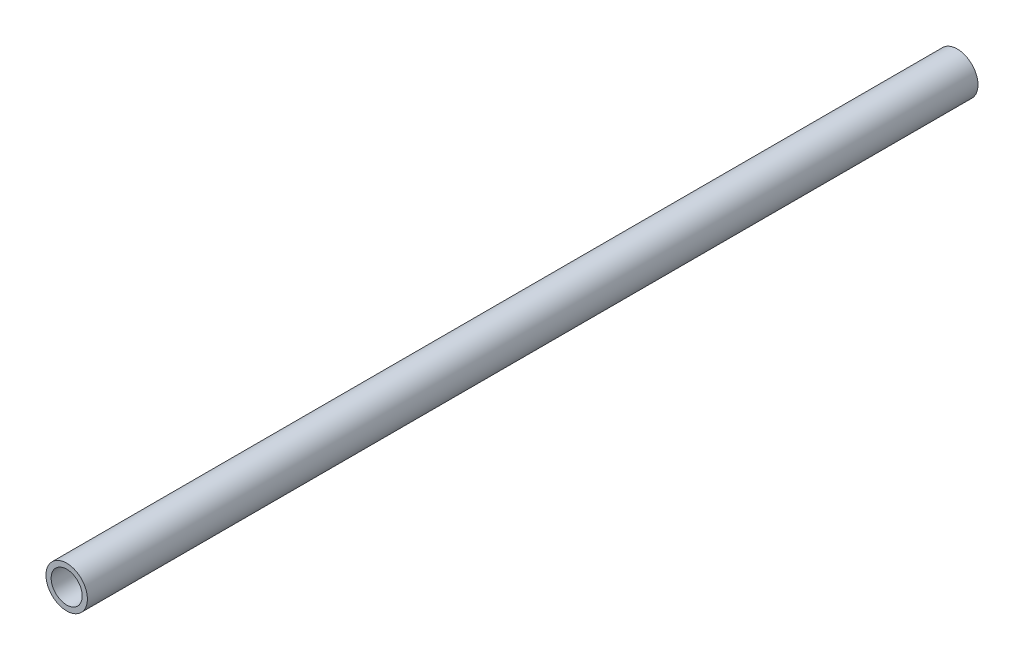
SolidWorks part; units mm, degrees
material "PC High Viscosity"
ref_plane "Front Plane" through (0, 0, 0) normal (0, 0, 1) x (1, 0, 0)
ref_plane "Top Plane" through (0, 0, 0) normal (0, 1, 0) x (1, 0, 0)
ref_plane "Right Plane" through (0, 0, 0) normal (1, 0, 0) x (0, 0, -1)
sketch "Sketch2" plane through (0, 0, 0) normal (0, 0, 1) x (1, 0, 0)
  circle A0 centre (0, 0) radius 9.525
  circle A1 centre (0, 0) radius 12.7
  dimension "D1" = 25.4
  dimension "D2" = 19.05
extrude "Boss-Extrude1" add sketch "Sketch2" along normal mid plane 546.1
